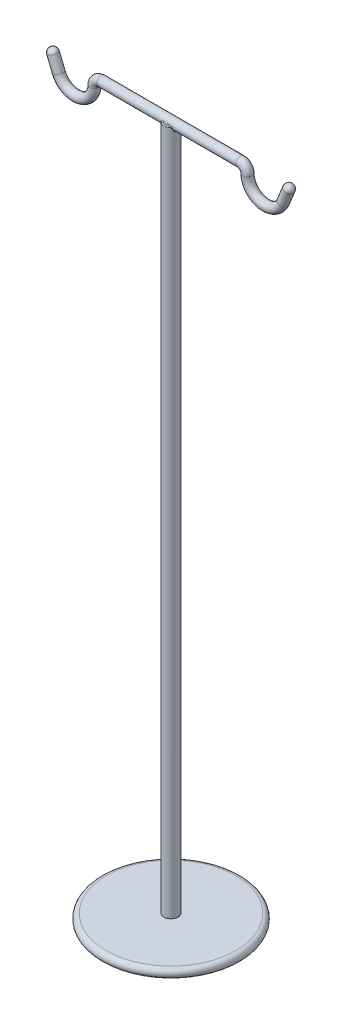
SolidWorks part; units mm, degrees
ref_plane "Front Plane" through (0, 0, 0) normal (0, 0, 1) x (1, 0, 0)
ref_plane "Top Plane" through (0, 0, 0) normal (0, 1, 0) x (1, 0, 0)
ref_plane "Right Plane" through (0, 0, 0) normal (1, 0, 0) x (0, 0, -1)
sketch "Sketch1" plane through (0, 0, 0) normal (0, 0, 1) x (1, 0, 0)
  line L0 (150, 0) -> (-150, 0)
  line L1 (0, 0) -> (0, -1500)
  line L2 (242.081, -30) -> (258.2618, 10)
  line L3 (-242.081, -30) -> (-258.2618, 10)
  arc A0 (150, 0) -> (165, -15) centre (150, -15) cw
  arc A1 (165, -15) -> (242.081, -30) centre (205, -15) ccw
  arc A2 (-165, -15) -> (-242.081, -30) centre (-205, -15) cw
  arc A3 (-150, 0) -> (-165, -15) centre (-150, -15) ccw
  point P4 (0, 0)
  point P11 (235.3046, -13.7428)
  point P13 (174.561, -20.3354)
  point P14 (165, -15)
  point P15 (220.3262, -20.9738)
  point P16 (240.986, 20.8623)
  point P17 (243.6071, -25.4638)
  dimension "D3" = 15
  dimension "D4" = 40
  dimension "D5" = 15
  dimension "D1" = 1500
  dimension "D2" = 300
  dimension "D6" = 10
sweep "Sweep1" add path "Sketch1" circular profile diameter 30 parameters "D3"=30
sweep "Sweep2" add path "Sketch1<3>" circular profile diameter 20 parameters "D3"=20
sketch "Sketch1<3>" plane through (0, 0, 0) normal (0, 0, 1) x (1, 0, 0) same geometry as "Sketch1"
fillet "Fillet1" radius 2 6 edges at (-14.9988, -9.9982, -0.1891) (14.9988, -9.9982, 0.1891) (0, 0, 15) (0, 0, -15) (0, 0, 10) (0, 0, -10)
fillet "Fillet2" radius 10 2 edges at (248.9915, 13.75, 0) (-248.9915, 13.75, 0)
sketch "Sketch14" plane through (0, 0, 0) normal (0, 0, 1) x (1, 0, 0)
  line L0 (0, -1500) -> (0, -51500) construction
  line L1 (-15, -1500) -> (15, -1500) construction
  line L2 (0, -1500) -> (140, -1500)
  line L3 (0, -1480) -> (0, -1500)
  line L4 (140, -1480) -> (0, -1480)
  arc A0 (140, -1500) -> (140, -1480) centre (140, -1490) ccw
  point P4 (0, -1500)
  dimension "D1" = 20
  dimension "D2" = 150
revolve "Revolve1" add sketch "Sketch14" angle 360 about L0
